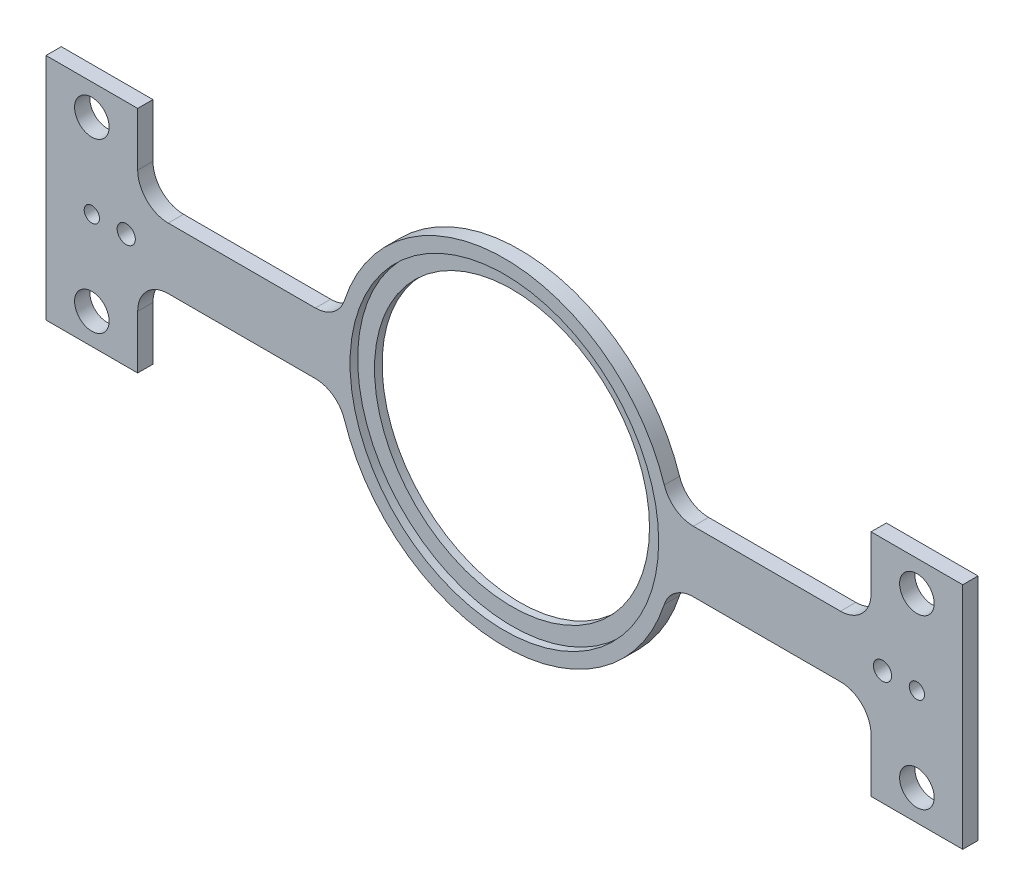
SolidWorks part; units mm, degrees
material "Commercially Pure CP-Ti UNS R50400 (SS)"
ref_plane "Front Plane" through (0, 0, 0) normal (0, 0, 1) x (1, 0, 0)
ref_plane "Top Plane" through (0, 0, 0) normal (0, 1, 0) x (1, 0, 0)
ref_plane "Right Plane" through (0, 0, 0) normal (1, 0, 0) x (0, 0, -1)
sketch "Sketch1" plane through (0, 0, 0) normal (0, 0, 1) x (1, 0, 0)
  line L0 (10.8167, 2) -> (24, 2)
  line L1 (24, 2) -> (24, 7.5)
  line L2 (24, 7.5) -> (30, 7.5)
  line L3 (30, 7.5) -> (30, -7.5)
  line L4 (30, -7.5) -> (24, -7.5)
  line L5 (24, -7.5) -> (24, -2)
  line L6 (24, -2) -> (10.8167, -2)
  line L7 (0, 0) -> (30, 0) construction
  line L8 (0, 0) -> (0, 25.3198) construction
  line L9 (-30, -7.5) -> (-24, -7.5)
  line L10 (-24, -7.5) -> (-24, -2)
  line L11 (-24, -2) -> (-10.8167, -2)
  line L12 (-24, 7.5) -> (-30, 7.5)
  line L13 (-30, 7.5) -> (-30, -7.5)
  line L14 (-24, 2) -> (-24, 7.5)
  line L15 (-10.8167, 2) -> (-24, 2)
  arc A0 (10.8167, 2) -> (-10.8167, 2) centre (0, 0) ccw
  circle A1 centre (0, 0) radius 9
  arc A2 (-10.8167, -2) -> (10.8167, -2) centre (0, 0) ccw
  dimension "D1" = 22
  dimension "D2" = 18
  dimension "D3" = 30
  dimension "D4" = 6
  dimension "D5" = 15
  dimension "D6" = 2
  dimension "D7" = 2
extrude "Boss-Extrude1" add sketch "Sketch1" along normal blind 1
sketch "Sketch2" plane through (0, 0, 1) normal (0, 0, 1) x (1, 0, 0)
  circle A0 centre (0, 0) radius 10.1
  dimension "D1" = 20.2
extrude "Cut-Extrude1" cut sketch "Sketch2" against normal blind 0.5
ref_plane "Plane1" through (0, 0, 0.5) normal (0, 0, 1) x (1, 0, 0)
ref_axis "Axis1" through (-33, 0, 0.5) along (1, 0, 0)
sketch "Sketch3" plane through (30, 0, 0) normal (1, 0, 0) x (0, 0, -1)
  line L0 (-0.5, 7.5) -> (0, 7.5)
  line L1 (-1, 7.5) -> (0, 7.5) construction
  line L2 (0, 7.5) -> (0, 7)
  line L3 (0, -7.5) -> (0, 7.5) construction
  line L4 (0, 7) -> (-0.5, 7.5)
  dimension "D1" = 0.5
extrude "Cut-Extrude2" [suppressed] cut sketch "Sketch3" against normal blind 4
sketch "Sketch6" plane through (0, 0, 0) normal (0, 0, -1) x (-1, 0, 0)
  line L0 (33, 0) -> (-33, 0) construction
  line L1 (-27, -7.5) -> (-27, 0) construction
  line L2 (-24, -7.5) -> (-30, -7.5) construction
  line L3 (27, -7.5) -> (27, 0) construction
  line L4 (30, -7.5) -> (24, -7.5) construction
  circle A0 centre (-27, 0) radius 0.5
  circle A1 centre (27, 0) radius 0.5
  dimension "D1" = 1
extrude "Cut-Extrude3" cut sketch "Sketch6" against normal through all
sketch "Sketch10" plane through (0, 0, 0) normal (0, 0, -1) x (-1, 0, 0)
  point P0 (-27, 0)
  point P1 (27, 0)
hole_wizard "#1 Clearance Hole1" positions "Sketch7" profile "Sketch9" hole size "#1" standard "ANSI Inch" end condition through all
sketch "Sketch7" plane through (0, 0, 0) normal (0, 0, -1) x (-1, 0, 0)
  line L0 (-27, 5.5) -> (-27, -5.5) construction
  line L1 (27, 5.5) -> (27, -5.5) construction
  point P0 (-27, -5.5)
  point P2 (-27, 5.5)
  point P4 (27, 5.5)
  point P6 (27, -5.5)
  dimension "D1" = 11
sketch "Sketch9" plane through (27, -5.5, 0) normal (1, 0, 0) x (0, 1, 0)
  line L0 (0, 0) -> (0, 1)
  line L1 (0, 1) -> (1.1303, 1)
  line L2 (1.1303, 1) -> (1.1303, 0)
  line L5 (1.1303, 0) -> (0, 0)
  line L11 (0, -6.35) -> (0, 107.95) construction
  dimension "Thru Hole Dia." = 2.2606
  dimension "Thru Hole Depth" = 1
hole_wizard "#0-80 Tapped Hole1" positions "Sketch13" profile "Sketch14" tap size "#0-80" standard "ANSI Inch" end condition through all
sketch "Sketch13" plane through (0, 0, 0) normal (0, 0, -1) x (-1, 0, 0)
  line L0 (33, 0) -> (-33, 0) construction
  line L1 (-24, 7.5) -> (-24, 2) construction
  line L2 (24, 2) -> (24, 7.5) construction
  point P0 (-24.75, 0)
  point P4 (24.75, 0)
  dimension "D1" = 0.75
  dimension "D2" = 0.75
sketch "Sketch14" plane through (24.75, 0, 0) normal (1, 0, 0) x (0, 1, 0)
  line L0 (0, 0) -> (0, 1)
  line L1 (0, 1) -> (0.5956, 1)
  line L2 (0.5956, 1) -> (0.5956, 0)
  line L5 (0.5956, 0) -> (0, 0)
  line L11 (0, -6.35) -> (0, 107.95) construction
  dimension "Thru Tap Drill Dia." = 1.1913
  dimension "Thru Tap Drill Depth" = 1
cosmetic thread "Hole Thread1" parameters "D2"=1.524
cosmetic thread "Hole Thread2" parameters "D2"=1.524
fillet "Fillet1" radius 2 8 edges at (-24, -2, 0.5) (-10.8167, -2, 0.5) (10.8167, -2, 0.5) (24, -2, 0.5) (-10.8167, 2, 0.5) (24, 2, 0.5) (10.8167, 2, 0.5) (-24, 2, 0.5)
ref_plane "Plane2" [suppressed] through (0, -0.25, 0.25) normal (0, 0.7071, -0.7071) x (1, 0, 0)
sketch "Sketch4" [suppressed] plane through (0, -0.25, 0.25) normal (0, 0.7071, -0.7071) x (1, 0, 0)
  line L0 (-33, -0.3536) -> (33, -0.3536) construction
  circle A0 centre (0, -0.3536) radius 2
  dimension "D1" = 4
extrude "Boss-Extrude2" [suppressed] add sketch "Sketch4" along normal blind 81 separate body
ref_plane "Plane3" [suppressed] through (0, 0.25, 0.25) normal (0, 0.7071, 0.7071) x (1, 0, 0)
sketch "Sketch5" [suppressed] plane through (0, 0.25, 0.25) normal (0, 0.7071, 0.7071) x (1, 0, 0)
  line L0 (-33, -0.3536) -> (33, -0.3536) construction
  circle A0 centre (0, -0.3536) radius 2
  dimension "D1" = 4
extrude "Boss-Extrude3" [suppressed] add sketch "Sketch5" against normal blind 81
sketch "Sketch15" plane through (0, 0, 0.5) normal (0, 0, 1) x (1, 0, 0)
  line L0 (0, 13.7007) -> (0, -13.7007) construction
